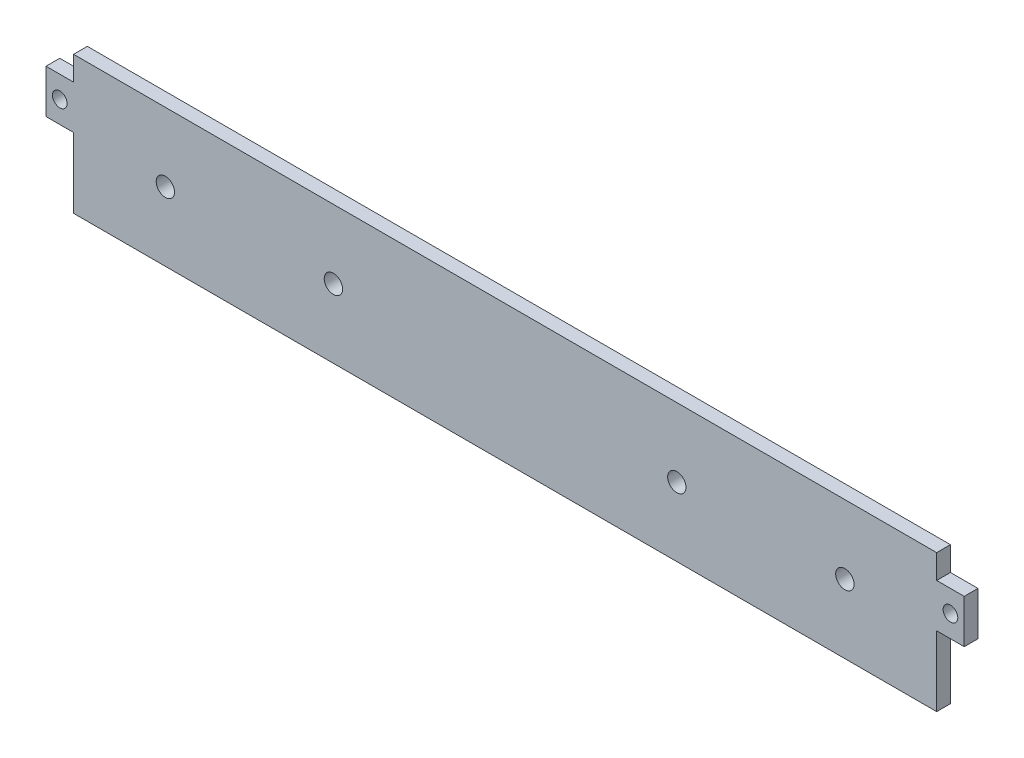
SolidWorks part; units mm, degrees
material "Balsa"
ref_plane "Plano frontal" through (0, 0, 0) normal (0, 0, 1) x (1, 0, 0)
ref_plane "Plano superior" through (0, 0, 0) normal (0, 1, 0) x (1, 0, 0)
ref_plane "Plano direito" through (0, 0, 0) normal (1, 0, 0) x (0, 0, -1)
sketch "Esboço1" plane through (0, 0, 0) normal (0, 0, 1) x (1, 0, 0)
  line L0 (-94, 0.25) -> (-94, -15)
  line L1 (-94, 15) -> (94, 15)
  line L2 (-94, 15) -> (-94, 9.75)
  line L3 (-94, -15) -> (94, -15)
  line L4 (94, 15) -> (94, 9.75)
  line L5 (-94, 15) -> (94, -15) construction
  line L6 (-94, -15) -> (94, 15) construction
  line L7 (-94, 9.75) -> (-100, 9.75)
  line L8 (0, 15) -> (0, -15) construction
  line L9 (-94, 0.25) -> (-100, 0.25)
  line L10 (-100, 9.75) -> (-100, 0.25)
  line L11 (94, 9.75) -> (100, 9.75)
  line L12 (94, 0.25) -> (100, 0.25)
  line L13 (100, 9.75) -> (100, 0.25)
  line L14 (94, 0.25) -> (94, -15)
  line L15 (-100, 9.75) -> (-94, 0.25) construction
  circle A0 centre (-97, 5) radius 1.6
  circle A1 centre (97, 5) radius 1.6
  circle A2 centre (-74, 0) radius 2
  circle A3 centre (-37.4, 0) radius 2
  circle A4 centre (37.4, 0) radius 2
  circle A5 centre (74, 0) radius 2
  point P0 (0, 0)
  dimension "D6" = 3.2
  dimension "D7" = 4
  dimension "D1" = 188
  dimension "D2" = 30
  dimension "D3" = 9.5
  dimension "D4" = 6
  dimension "D5" = 5.25
  dimension "D8" = 36.6
  dimension "D9" = 15
  dimension "D10" = 20
extrude "Ressalto-extrusão1" add sketch "Esboço1" along normal blind 3
